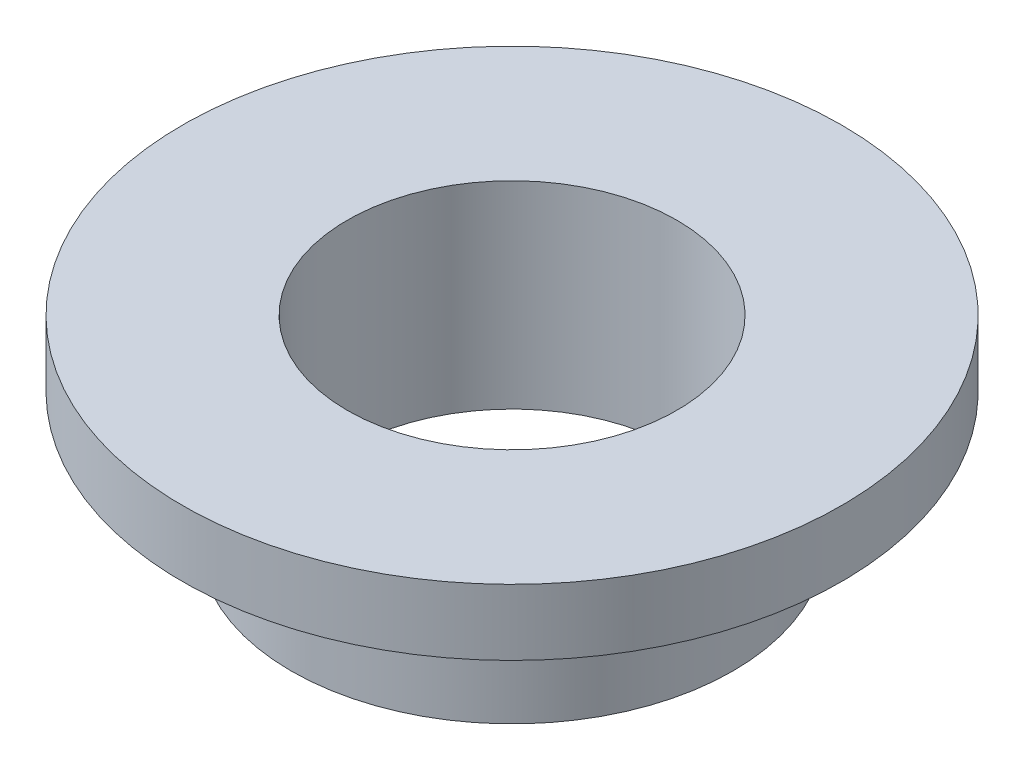
SolidWorks part; units mm, degrees
material "Сталь ШХ15 ГОСТ 801-78"
ref_plane "Plane1" through (0, 0, 0) normal (0, 0, 1) x (1, 0, 0)
ref_plane "Plane2" through (0, 0, 0) normal (0, 1, 0) x (1, 0, 0)
ref_plane "Plane3" through (0, 0, 0) normal (1, 0, 0) x (0, 0, -1)
sketch "Эскиз1" plane through (0, 0, 0) normal (0, 0, 1) x (1, 0, 0)
  line L6 (0, 0) -> (0, 6.4893) construction
  line L7 (5, -0.354) -> (5, 5.646)
  line L8 (5, 5.646) -> (10, 5.646)
  line L9 (10, 5.646) -> (10, 3.646)
  line L10 (10, 3.646) -> (6.7, 3.646)
  line L11 (6.7, 3.646) -> (6.7, -0.354)
  line L12 (6.7, -0.354) -> (5, -0.354)
  dimension "D1" = 5
  dimension "D2" = 6.7
  dimension "D3" = 10
  dimension "D4" = 2
  dimension "D5" = 6
revolve "Повернуть1" add sketch "Эскиз1" angle 360 about L6
